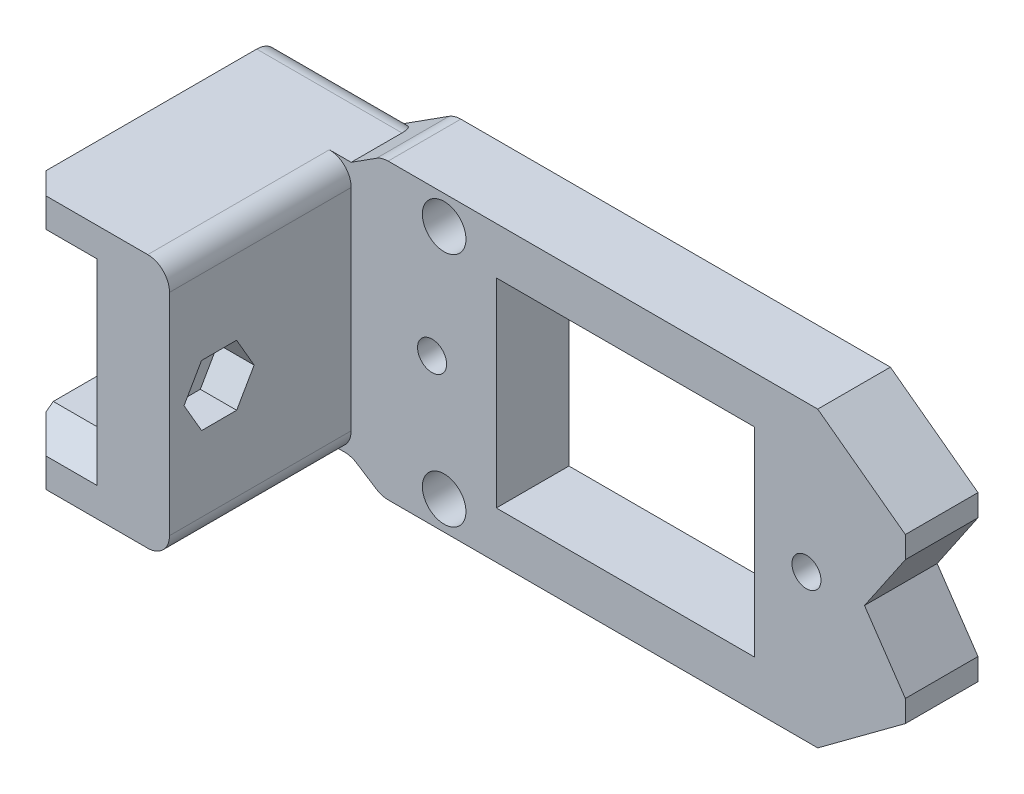
SolidWorks part; units mm, degrees
note: The reader was unsure of these and kept them because the rebuilt part matched: shared geometry of "草图3<3>".
ref_plane "前视基准面" through (0, 0, 0) normal (0, 0, 1) x (1, 0, 0)
ref_plane "上视基准面" through (0, 0, 0) normal (0, 1, 0) x (1, 0, 0)
ref_plane "右视基准面" through (0, 0, 0) normal (1, 0, 0) x (0, 0, -1)
other "Configuration Table"
sketch "草图3" plane through (0, 0, 0) normal (0, 0, 1) x (1, 0, 0)
  line L0 (0, 0) -> (59.5123, 0) construction
  line L1 (59.5123, 0) -> (65.1343, 8.2699)
  line L2 (65.1343, 8.2699) -> (65.1343, 11.2699)
  line L3 (65.1343, 11.2699) -> (53.0773, 20.1934)
  line L4 (53.0773, 20.1934) -> (-6.9227, 20.1934)
  line L5 (-6.9227, 20.1934) -> (-11.1353, 17.5)
  line L6 (-11.1353, 17.5) -> (-31.1353, 17.5)
  line L7 (-31.1353, 17.5) -> (-31.1353, -17.5)
  line L8 (-11.1353, -17.5) -> (-31.1353, -17.5)
  line L9 (-6.9227, -20.1934) -> (-11.1353, -17.5)
  line L10 (53.0773, -20.1934) -> (-6.9227, -20.1934)
  line L11 (65.1343, -11.2699) -> (53.0773, -20.1934)
  line L12 (65.1343, -8.2699) -> (65.1343, -11.2699)
  line L13 (59.5123, 0) -> (65.1343, -8.2699)
  line L14 (8.8385, -13.7143) -> (44.349, -13.7143)
  line L15 (44.349, -13.7143) -> (44.349, 13.7143)
  line L16 (8.8385, -13.7143) -> (8.8385, 0)
  line L17 (8.8385, 13.7143) -> (8.8385, 0)
  line L18 (8.8385, 13.7143) -> (44.349, 13.7143)
  line L19 (-11.1353, 17.5) -> (-11.1353, -17.5)
  circle A0 centre (1.6603, 16.2351) radius 3
  circle A1 centre (51.5266, 0) radius 2
  circle A2 centre (1.6603, -16.2351) radius 3
  circle A3 centre (0, 0) radius 2
  point P11 (-31.1353, 0)
  point P18 (8.8385, -6.8571)
  point P21 (8.8385, 6.8571)
  point P24 (44.349, 0)
  point P28 (0, 0)
  dimension "D8" = 6
  dimension "D9" = 4
  dimension "D10" = 4
  dimension "D1" = 60
  dimension "D2" = 15
  dimension "D3" = 3
  dimension "D4" = 10
  dimension "D5" = 5
  dimension "D6" = 20
  dimension "D7" = 35
extrude "凸台-拉伸1" add sketch "草图3" along normal mid plane 10
extrude "凸台-拉伸2" add sketch "草图3<3>" along normal blind 30 and the other way blind 5 contours L19 L6 L7 L8
sketch "草图3<3>" plane through (0, 0, 0) normal (0, 0, 1) x (1, 0, 0) same geometry as "草图3"
sketch "草图4" plane through (-31.1353, 0, 0) normal (-1, 0, 0) x (0, 0, 1)
  line L0 (-5, 0) -> (30, 0) construction
  line L1 (-5, 17.5) -> (-5, -17.5) construction
  line L2 (30, 17.5) -> (30, -17.5) construction
  line L3 (0, -13.5) -> (0, 13.5)
  line L4 (0, 13.5) -> (7, 13.5)
  line L5 (7, 13.5) -> (11, 10.5)
  line L6 (11, 10.5) -> (14, 10.5)
  line L7 (14, 10.5) -> (14, 13.5)
  line L8 (14, 13.5) -> (30, 13.5)
  line L9 (-5, 17.5) -> (30, 17.5) construction
  line L10 (11, -10.5) -> (26, -10.5)
  line L11 (26, -10.5) -> (30, -13.5)
  line L13 (7, -13.5) -> (11, -10.5)
  line L14 (0, -13.5) -> (7, -13.5)
  point P25 (0, 0)
  dimension "D1" = 7
  dimension "D2" = 5
  dimension "D3" = 3
  dimension "D4" = 16
  dimension "D5" = 4
  dimension "D6" = 4
  dimension "D7" = 15
  dimension "D8" = 3
extrude "切除-拉伸1" cut sketch "草图4" against normal blind 10 and the other way through all
sketch "草图5" plane through (-21.1353, 0, 0) normal (-1, 0, 0) x (0, 0, 1)
  circle A0 centre (23.1783, 0) radius 2.5
  point P2 (0, 0)
  point P3 (23.1783, 0)
  dimension "D1" = 5
extrude "切除-拉伸2" cut sketch "草图5" against normal blind 5
sketch "草图7" plane through (-11.1353, 0, 0) normal (1, 0, 0) x (0, 0, -1)
  line L1 (-20.7595, -4.1753) -> (-18.3529, 0.0071)
  line L2 (-18.3529, 0.0071) -> (-20.7718, 4.1824)
  line L3 (-20.7718, 4.1824) -> (-25.5971, 4.1753)
  line L4 (-25.5971, 4.1753) -> (-28.0037, -0.0071)
  line L5 (-28.0037, -0.0071) -> (-25.5848, -4.1824)
  line L6 (-25.5848, -4.1824) -> (-20.7595, -4.1753)
  circle A0 centre (-23.1783, 0) radius 4.1789 construction
extrude "切除-拉伸3" cut sketch "草图7" against normal blind 5
fillet "圆角2" radius 3 1 edges at (-21.1353, -17.5, -5)
fillet "圆角3" radius 3 1 edges at (-21.1353, 17.5, -5)
fillet "圆角4" radius 3 2 edges at (-11.1353, 17.5, 17.5) (-11.1353, -17.5, 17.5)
fillet "圆角5" radius 3 2 edges at (-6.9227, 20.1934, 0) (-6.9227, -20.1934, 0)
fillet "圆角6" radius 3 2 edges at (-12.5096, -16.6213, -4.1213) (-11.1353, -17.5, 1.5)
chamfer "倒角1" distance 3 angle 45 2 edges at (-31.1353, 15.5, 30) (-31.1353, -15.5, 30)
